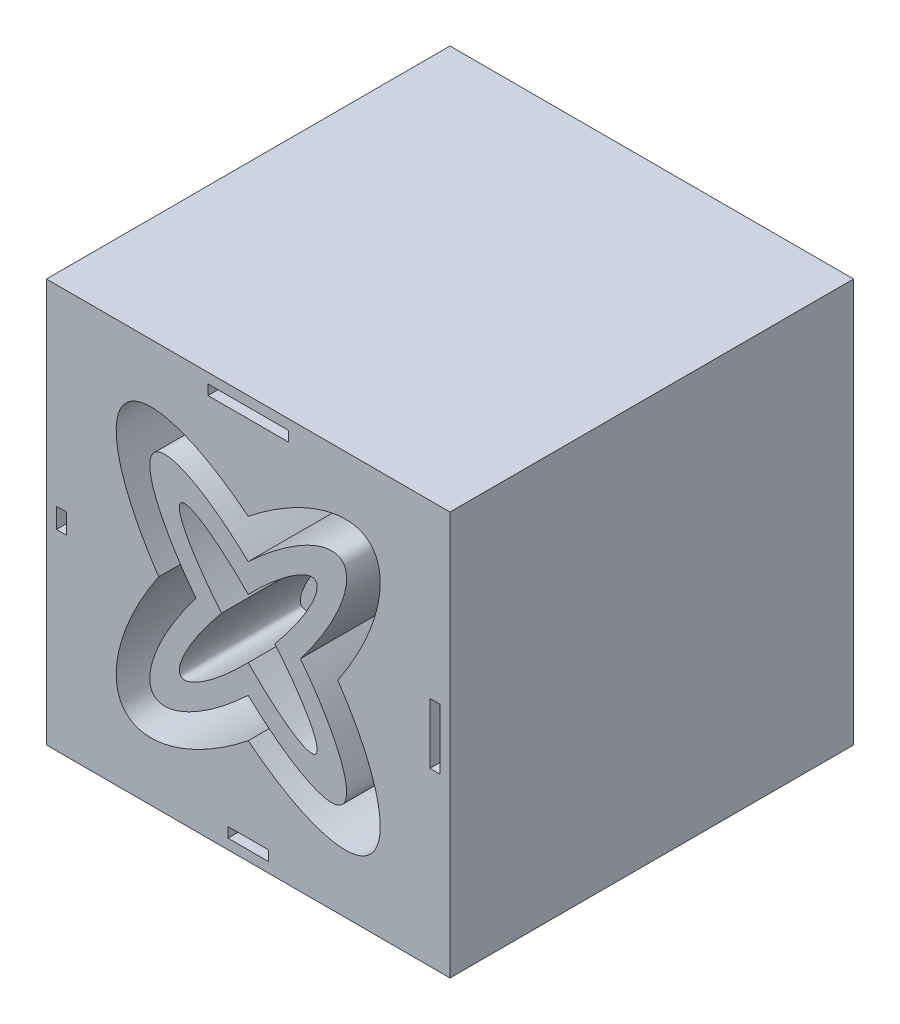
SolidWorks part; units mm, degrees
ref_plane "Plan de face" through (0, 0, 0) normal (0, 0, 1) x (1, 0, 0)
ref_plane "Plan de dessus" through (0, 0, 0) normal (0, 1, 0) x (1, 0, 0)
ref_plane "Plan de droite" through (0, 0, 0) normal (1, 0, 0) x (0, 0, -1)
sketch "Esquisse1" plane through (0, 0, 0) normal (0, 0, 1) x (1, 0, 0)
  line L1 (-100, 100) -> (100, 100)
  line L2 (-100, 100) -> (-100, -100)
  line L3 (-100, -100) -> (100, -100)
  line L4 (100, 100) -> (100, -100)
  point P4 (0, 100)
  point P6 (-100, 0)
  dimension "D1" = 200
  dimension "D2" = 200
extrude "Boss.-Extru.1" add sketch "Esquisse1" along normal blind 100 and the other way blind 100
sketch "Esquisse2" plane through (0, 0, 100) normal (0, 0, 1) x (1, 0, 0)
  line L0 (-100, -100) -> (100, -100) construction
  line L1 (10, -95) -> (-10, -95)
  line L2 (10, -95) -> (10, -90)
  line L3 (10, -90) -> (-10, -90)
  line L4 (-10, -95) -> (-10, -90)
  line L5 (95, -15) -> (90, -15)
  line L6 (95, -15) -> (95, 15)
  line L7 (95, 15) -> (90, 15)
  line L8 (90, -15) -> (90, 15)
  line L9 (-20, 95) -> (20, 95)
  line L10 (-20, 95) -> (-20, 90)
  line L11 (-20, 90) -> (20, 90)
  line L12 (20, 95) -> (20, 90)
  line L13 (-95, 5) -> (-90, 5)
  line L14 (-95, 5) -> (-95, -5)
  line L15 (-95, -5) -> (-90, -5)
  line L16 (-90, 5) -> (-90, -5)
  line L17 (100, -100) -> (100, 100) construction
  line L18 (100, 100) -> (-100, 100) construction
  line L19 (-100, 100) -> (-100, -100) construction
  ellipse E0 centre (0, 0) end of major axis (60, 67.082) minor radius 35
  ellipse E1 centre (0, 0) end of major axis (60, -67.082) minor radius 35
  ellipse E2 centre (0, 0) end of major axis (46.4018, -52.4162) minor radius 20.0006
  ellipse E3 centre (0, 0) end of major axis (46.4444, 52.3767) minor radius 20.0004
  ellipse E4 centre (0, 0) end of major axis (-33.3376, 37.2726) minor radius 10.0009
  ellipse E5 centre (0, 0) end of major axis (-33.3328, -37.2742) minor radius 10.0006
  point P50 (0, -95)
  point P53 (0, -100)
  point P54 (95, 0)
  point P57 (100, 0)
  point P58 (0, 95)
  point P61 (0, 100)
  point P62 (-95, 0)
  point P65 (-100, 0)
  dimension "D1" = 70
  dimension "D2" = 180
  dimension "D3" = 180
  dimension "D4" = 70
  dimension "D5" = 40
  dimension "D6" = 40
  dimension "D7" = 20
  dimension "D8" = 20
  dimension "D9" = 15
  dimension "D10" = 15
  dimension "D11" = 20
  dimension "D12" = 10
  dimension "D13" = 20
  dimension "D14" = 10
  dimension "D15" = 0
  dimension "D16" = 20
  dimension "D17" = 5
  dimension "D18" = 5
  dimension "D19" = 0
  dimension "D20" = 30
  dimension "D21" = 5
  dimension "D22" = 5
  dimension "D23" = 0
  dimension "D24" = 5
  dimension "D25" = 5
  dimension "D26" = 40
  dimension "D27" = 0
  dimension "D28" = 10
  dimension "D29" = 5
  dimension "D30" = 5
extrude "Enlèv. mat.-Extru.2" cut sketch "Esquisse2" against normal blind 60 contours E3 E1 E0 | E3 E2 E0 E1 | E2 E0 E1 | E3 E1 E0 E2 | E3 E1 E0 | E3 E2 E0 E1 | E2 E0 E1 | E3 E1 E0 E2 | E1 E5 E2 | E1 E5 | E2 E5 E4 | E4 E5 | E4 E5 E2 | E2 E5 E1 | E1 E5 | E0 E4 | E3 E4 E0 | E5 E4 E3 | E5 E4 E3 | E0 E4 E3 | E0 E4 | L16 L13 L14 L15 | L12 L9 L10 L11 | L4 L1 L2 L3 | L8 L7 L6 L5 region at (0, -92.5, 100) region at (0, 92.5, 100) region at (-92.5, 0, 100) region at (60.4857, 32.6846, 100) region at (0.009, 38.5656, 100) region at (-6.3268, 44.1485, 100) region at (60.4857, -32.6846, 100) region at (35.1932, -0.0087, 100) region at (-40.5543, -7.0539, 100) region at (-35.1932, 0.0087, 100) region at (-18.2859, 20.2526, 100) region at (-27.5588, 30.5763, 100) region at (27.5556, 30.5783, 100) region at (18.286, 20.2539, 100) region at (-0.009, -38.5656, 100) region at (27.5588, -30.5763, 100) region at (18.2859, -20.2526, 100) region at (-10.0272, 11.1117, 100) region at (10.0254, 11.1151, 100) region at (-18.286, -20.2539, 100) region at (-27.5556, -30.5783, 100) region at (10.0272, -11.1117, 100) region at (0, 0, 100) region at (-10.0254, -11.1151, 100)
mirror "Symétrie2" about plane through (0, 0, 0) normal (0, 0, 1) of "Enlèv. mat.-Extru.2"
scale "Echelle1" scale about centroid uniform scaling yes scale factor 0.004
